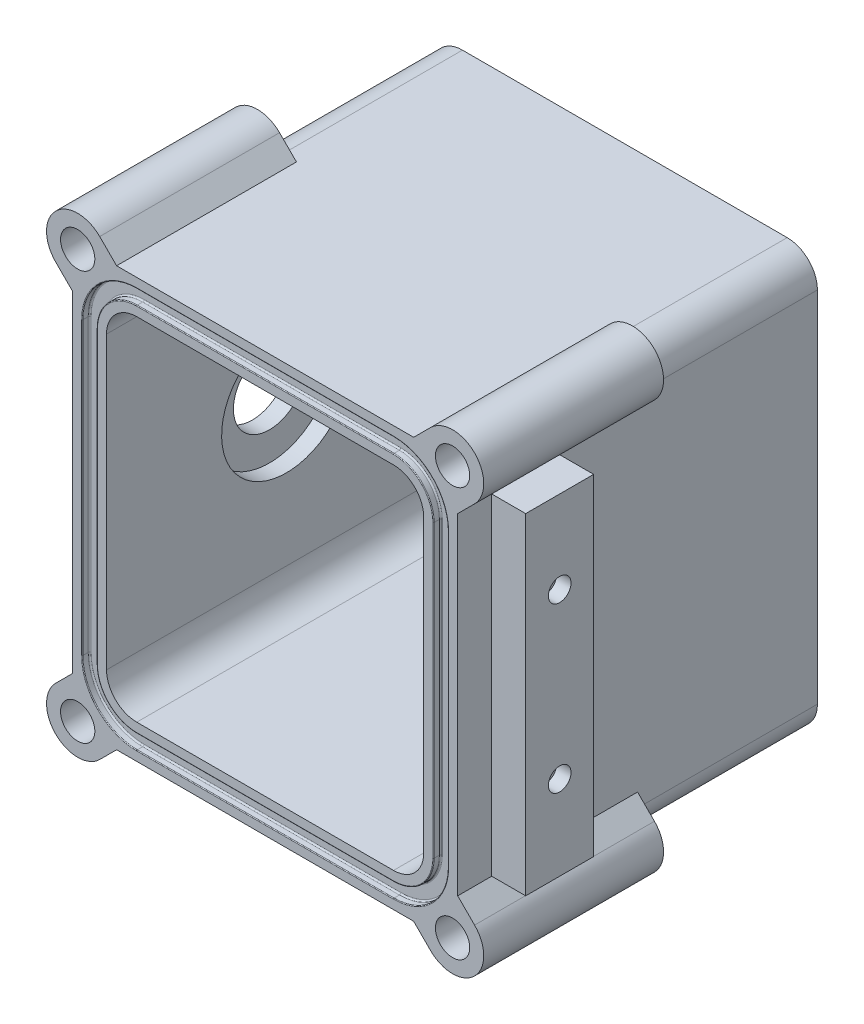
SolidWorks part; units mm, degrees
material "ABS"
ref_plane "X-Y Datum" through (0, 0, 0) normal (0, 0, 1) x (1, 0, 0)
ref_plane "X-Z Datum" through (0, 0, 0) normal (0, 1, 0) x (1, 0, 0)
ref_plane "Y-Z Datum" through (0, 0, 0) normal (1, 0, 0) x (0, 0, -1)
sketch "Sketch1" plane through (0, 0, 0) normal (0, 0, 1) x (1, 0, 0)
  line L0 (-34, -37) -> (-34, -16.68)
  line L1 (34, 37) -> (-34, 37)
  line L2 (34, 37) -> (34, -37)
  line L3 (34, -37) -> (-34, -37)
  line L5 (34, 37) -> (-34, -37) construction
  line L6 (34, -37) -> (-34, 37) construction
  line L7 (55.1739, 0) -> (-55.1739, 0) construction
  line L8 (-34, 37) -> (-34, 16.68)
  line L9 (-34, 16.68) -> (-34, -16.68)
  arc A0 (-34, -16.68) -> (-34, 16.68) centre (-14.8444, 0) cw construction
  point P0 (0, 0)
  dimension "D2" = 25.4
  dimension "D1" = 74
  dimension "D3" = 20.32
  dimension "D4" = 68
extrude "Boss-Extrude1" add sketch "Sketch1" along normal mid plane 63.5
shell "Shell1" thickness 6 removed face at (0, 0, 31.75)
fillet "Fillet1" radius 5.334 8 edges at (34, 37, 0) (34, -37, 0) (-34, -37, 0) (-34, 37, 0) (28, 31, 3) (28, -31, 3) (-28, -31, 3) (-28, 31, 3)
sketch "Sketch2" plane through (0, 0, 31.75) normal (0, 0, 1) x (1, 0, 0)
  line L21 (32.2827, -25.666) -> (32.2827, 25.666)
  line L22 (22.666, 35.2827) -> (-22.666, 35.2827)
  line L23 (-32.2827, 25.666) -> (-32.2827, -25.666)
  line L24 (-22.666, -35.2827) -> (22.666, -35.2827)
  line L25 (31, -25.666) -> (31, 25.666)
  line L26 (-22.666, -34) -> (22.666, -34)
  line L27 (-31, 25.666) -> (-31, -25.666)
  line L28 (22.666, 34) -> (-22.666, 34)
  line L29 (31, -25.666) -> (31, 25.666) construction
  line L30 (-22.666, -34) -> (22.666, -34) construction
  line L31 (-31, 25.666) -> (-31, -25.666) construction
  line L32 (22.666, 34) -> (-22.666, 34) construction
  line L33 (-29.7173, 25.666) -> (-29.7173, -25.666)
  line L34 (-22.666, -32.7173) -> (22.666, -32.7173)
  line L35 (29.7173, -25.666) -> (29.7173, 25.666)
  line L36 (22.666, 32.7173) -> (-22.666, 32.7173)
  arc A15 (32.2827, 25.666) -> (22.666, 35.2827) centre (22.666, 25.666) ccw
  arc A16 (-22.666, 35.2827) -> (-32.2827, 25.666) centre (-22.666, 25.666) ccw
  arc A17 (-32.2827, -25.666) -> (-22.666, -35.2827) centre (-22.666, -25.666) ccw
  arc A18 (22.666, -35.2827) -> (32.2827, -25.666) centre (22.666, -25.666) ccw
  arc A19 (31, 25.666) -> (22.666, 34) centre (22.666, 25.666) ccw
  arc A20 (22.666, -34) -> (31, -25.666) centre (22.666, -25.666) ccw
  arc A21 (-31, -25.666) -> (-22.666, -34) centre (-22.666, -25.666) ccw
  arc A22 (-22.666, 34) -> (-31, 25.666) centre (-22.666, 25.666) ccw
  arc A23 (31, 25.666) -> (22.666, 34) centre (22.666, 25.666) ccw construction
  arc A24 (22.666, -34) -> (31, -25.666) centre (22.666, -25.666) ccw construction
  arc A25 (-31, -25.666) -> (-22.666, -34) centre (-22.666, -25.666) ccw construction
  arc A26 (-22.666, 34) -> (-31, 25.666) centre (-22.666, 25.666) ccw construction
  arc A27 (-22.666, 32.7173) -> (-29.7173, 25.666) centre (-22.666, 25.666) ccw
  arc A28 (-29.7173, -25.666) -> (-22.666, -32.7173) centre (-22.666, -25.666) ccw
  arc A29 (22.666, -32.7173) -> (29.7173, -25.666) centre (22.666, -25.666) ccw
  arc A30 (29.7173, 25.666) -> (22.666, 32.7173) centre (22.666, 25.666) ccw
  dimension "D4" = 7.0513
  dimension "D5" = 2.5654
  dimension "D1" = 3
  dimension "D2" = 1.2827
  dimension "D3" = 1.2827
extrude "Cut-Extrude1" cut sketch "Sketch2" against normal blind 1.2954
fillet "Fillet2" radius 0.254 16 edges at (27.652, -30.652, 30.4546) (0, -32.7173, 30.4546) (-27.652, -30.652, 30.4546) (-29.7173, 0, 30.4546) (-27.652, 30.652, 30.4546) (0, 32.7173, 30.4546) (27.652, 30.652, 30.4546) (-29.466, 32.466, 30.4546) (0, 35.2827, 30.4546) (29.466, 32.466, 30.4546) (32.2827, 0, 30.4546) (29.466, -32.466, 30.4546) (0, -35.2827, 30.4546) (-29.466, -32.466, 30.4546) (29.7173, 0, 30.4546) (-32.2827, 0, 30.4546)
fillet "Fillet3" radius 0.127 16 edges at (-29.466, -32.466, 31.75) (-32.2827, 0, 31.75) (-29.466, 32.466, 31.75) (0, 35.2827, 31.75) (29.466, 32.466, 31.75) (32.2827, 0, 31.75) (29.466, -32.466, 31.75) (-27.652, -30.652, 31.75) (-29.7173, 0, 31.75) (-27.652, 30.652, 31.75) (0, 32.7173, 31.75) (27.652, 30.652, 31.75) (29.7173, 0, 31.75) (27.652, -30.652, 31.75) (0, -35.2827, 31.75) (0, -32.7173, 31.75)
sketch "Sketch3" plane through (0, 0, 31.75) normal (0, 0, 1) x (1, 0, 0)
  line L0 (22.666, -25.666) -> (37.7124, -40.7124) construction
  line L1 (29.2023, -39.9805) -> (26.2218, -37)
  line L2 (-28.666, -37) -> (28.666, -37) construction
  line L3 (22.666, -25.666) -> (0, 0)
  line L5 (34, -29.2218) -> (36.9805, -32.2023)
  line L6 (34, -31.666) -> (34, 31.666) construction
  arc A0 (22.666, -35.4097) -> (32.4097, -25.666) centre (22.666, -25.666) ccw construction
  arc A1 (22.666, -35.4097) -> (32.4097, -25.666) centre (22.666, -25.666) ccw
  circle A2 centre (33.0914, -36.0914) radius 3.025
  circle A3 centre (33.0914, -36.0914) radius 5.5
  point P7 (29.5558, -32.5558)
  arc M9 (32.4097, -25.666) -> (22.666, -35.4097) centre (22.666, -25.666) cw
  line M14 (-28.666, -37) -> (28.666, -37)
  arc M15 (28.666, -37) -> (34, -31.666) centre (28.666, -31.666) ccw
  line M16 (34, -31.666) -> (34, 31.666)
  dimension "D1" = 6.05
  dimension "D3" = 11
  dimension "D2" = 5
extrude "Boss-Extrude2" add sketch "Sketch3" against normal blind 31.75 contours L0 A2 A3 M15 M14 | A2 L0 A3 M16 M15 | L0 A2 M15 | L0 A2 M15 | A2 L0 M15 | A3 M14 | A3 M16 | A1 L0 A2 A3 M15 M16 | L0 A2 M15 | L0 A3 A2 M9 M14 M15 region at (32.0118, -32.0896, 31.75) region at (29.0896, -35.0118, 31.75) region at (32.4421, -34.0333, 31.75) region at (31.0333, -35.4421, 31.75) region at (34.789, -30.4552, 31.75) region at (36.5269, -35.0577, 31.75) region at (32.0577, -39.5269, 31.75) region at (27.4552, -37.789, 31.75) region at (34.5525, -35.5923, 31.75) region at (32.5923, -37.5525, 31.75)
sketch "Sketch4" plane through (0, 0, 31.75) normal (0, 0, 1) x (1, 0, 0)
  circle A0 centre (33.0914, -36.0914) radius 3.025 construction
  circle A1 centre (33.0914, -36.0914) radius 3.025
  dimension "D1" = 6.05
extrude "Cut-Extrude2" cut sketch "Sketch4" against normal blind 9
mirror "Mirror1" about plane through (0, 0, 0) normal (0, 1, 0) of "Cut-Extrude2", "Boss-Extrude2"
mirror "Mirror2" about plane through (0, 0, 0) normal (1, 0, 0) of "Mirror1", "Cut-Extrude2", "Boss-Extrude2"
sketch "Sketch8" plane through (-34, 0, 0) normal (-1, 0, 0) x (0, 0, 1)
  line L0 (19.75, 29.2218) -> (19.75, -29.2218) construction
  line L11 (25.75, 29.2218) -> (25.75, -29.2218)
  line L12 (0, 29.2218) -> (31.75, 29.2218) construction
  line L13 (0, -29.2218) -> (31.75, -29.2218) construction
  line L14 (25.75, 29.2218) -> (13.75, 29.2218)
  line L15 (13.75, 29.2218) -> (13.75, -29.2218)
  line L16 (13.75, -29.2218) -> (25.75, -29.2218)
  line L17 (13.75, 0) -> (25.75, 0) construction
  line L18 (25.75, 29.2218) -> (13.75, 29.2218)
  line L19 (25.75, -29.2218) -> (13.75, -29.2218)
  point P0 (0, 0)
  line M1 (31.75, 29.2218) -> (0, 29.2218)
  line M7 (0, -29.2218) -> (31.75, -29.2218)
extrude "Boss-Extrude3" add sketch "Sketch8" along normal blind 6 contours L15 L11 M1 M7 region at (-34, 0, 19.75)
sketch "Sketch12" plane through (-40, 0, 0) normal (-1, 0, 0) x (0, 0, 1)
  line L0 (19.75, 29.2218) -> (19.75, -29.2218) construction
  line L1 (25.75, 29.2218) -> (13.75, 29.2218) construction
  line L2 (13.75, -29.2218) -> (25.75, -29.2218) construction
  line L3 (13.75, 0) -> (25.75, 0) construction
  line L4 (13.75, 29.2218) -> (13.75, -29.2218) construction
  line L5 (25.75, 29.2218) -> (25.75, -29.2218) construction
  circle A0 centre (19.75, 14.6168) radius 2
  circle A1 centre (19.75, -14.3392) radius 2
  dimension "D1" = 14.605
  dimension "D3" = 4
  dimension "D2" = 28.956
extrude "Cut-Extrude6" cut sketch "Sketch12" against normal blind 2.54
sketch "Sketch13" plane through (-34, 0, 0) normal (-1, 0, 0) x (0, 0, 1)
  line L0 (-31.75, 0) -> (31.75, 0) construction
  line L3 (-31.75, 31.666) -> (-31.75, -31.666) construction
  line L4 (31.75, 29.2218) -> (31.75, -29.2218) construction
  circle A0 centre (0, 0) radius 6.35
  dimension "D2" = 12.7
extrude "Cut-Extrude10" cut sketch "Sketch13" against normal blind 6 contours A0 | A0 region at (-34, 0, 0)
sketch "Sketch16" plane through (-28, 0, 0) normal (1, 0, 0) x (0, 0, -1)
  circle A0 centre (0, 0) radius 11.43
  dimension "D1" = 22.86
extrude "Cut-Extrude14" cut sketch "Sketch16" against normal blind 3
mirror "Mirror5" about plane through (0, 0, 0) normal (1, 0, 0) of "Boss-Extrude3"
mirror "Mirror6" about plane through (0, 0, 0) normal (1, 0, 0) of "Cut-Extrude6"
